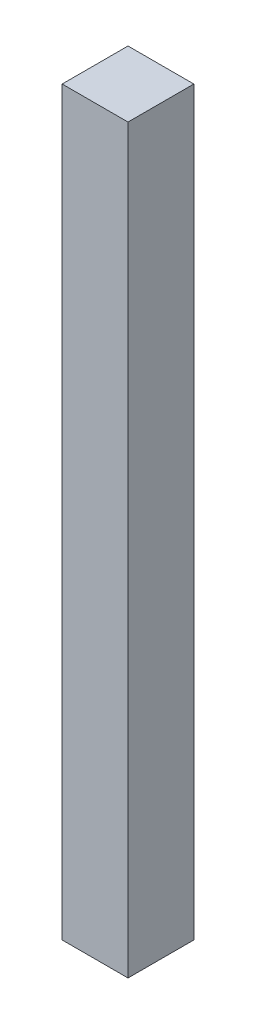
SolidWorks part; units mm, degrees
ref_plane "Front Plane" through (0, 0, 0) normal (0, 0, 1) x (1, 0, 0)
ref_plane "Top Plane" through (0, 0, 0) normal (0, 1, 0) x (1, 0, 0)
ref_plane "Right Plane" through (0, 0, 0) normal (1, 0, 0) x (0, 0, -1)
sketch "Sketch1" plane through (0, 0, 0) normal (0, 1, 0) x (1, 0, 0)
  line L1 (0, 0) -> (25.4, 0)
  line L2 (0, 0) -> (0, 25.4)
  line L3 (0, 25.4) -> (25.4, 25.4)
  line L4 (25.4, 0) -> (25.4, 25.4)
  dimension "D1" = 25.4
  dimension "D2" = 25.4
extrude "Boss-Extrude1" add sketch "Sketch1" along normal blind 609.6
sketch "Sketch3" plane through (0, 0, -25.4) normal (0, 0, -1) x (-1, 0, 0)
  line L0 (0, 609.6) -> (0, 0) construction
  line L1 (0, 466.3042) -> (-25.4, 466.3042)
  line L2 (0, 466.3042) -> (0, 609.6)
  line L3 (0, 609.6) -> (-25.4, 609.6)
  line L4 (-25.4, 466.3042) -> (-25.4, 609.6)
  line L6 (-25.4, 466.3042) -> (0, 466.3042) construction
extrude "Cut-Extrude1" [suppressed] cut sketch "Sketch3" against normal up to surface (25.4 mm away) up to face at (12.7, 304.8, 0)
sketch "Sketch4" [suppressed] plane through (0, 0, 0) normal (0, 0, 1) x (1, 0, 0)
  line L0 (0, 609.6) -> (0, 0) construction
  line L1 (0, 276.4933) -> (25.4, 276.4933)
  line L2 (0, 276.4933) -> (0, 609.6)
  line L3 (0, 609.6) -> (25.4, 609.6)
  line L4 (25.4, 276.4933) -> (25.4, 609.6)
  line L6 (0, 276.4933) -> (25.4, 276.4933) construction
extrude "Cut-Extrude2" [suppressed] cut sketch "Sketch4" against normal up to surface (430.6021 mm away) up to face at (12.7, 304.8, -25.4)
sketch "Sketch5" plane through (0, 0, -25.4) normal (0, 0, -1) x (-1, 0, 0)
  line L0 (0, 609.6) -> (0, 0) construction
  line L1 (0, 571.9407) -> (-25.4, 571.9407)
  line L2 (0, 571.9407) -> (0, 609.6)
  line L3 (0, 609.6) -> (-25.4, 609.6)
  line L4 (-25.4, 571.9407) -> (-25.4, 609.6)
extrude "Cut-Extrude3" cut sketch "Sketch5" against normal up to surface (25.4 mm away) up to face at (12.7, 304.8, 0)
sketch "Sketch6" [suppressed] plane through (0, 0, -25.4) normal (0, 0, -1) x (-1, 0, 0)
  line L0 (0, 609.6) -> (0, 0) construction
  line L1 (0, 553.696) -> (-25.4, 553.696)
  line L2 (0, 553.696) -> (0, 609.6)
  line L3 (0, 609.6) -> (-25.4, 609.6)
  line L4 (-25.4, 553.696) -> (-25.4, 609.6)
  line L6 (-25.4, 553.696) -> (0, 553.696) construction
extrude "Cut-Extrude4" [suppressed] cut sketch "Sketch6" against normal up to surface (25.4 mm away) up to face at (12.7, 285.9703, 0)
sketch "Sketch7" [suppressed] plane through (0, 0, 0) normal (0, 0, 1) x (1, 0, 0)
  line L0 (25.4, 609.6) -> (25.4, 0) construction
  line L1 (25.4, 422.1079) -> (0, 422.1079)
  line L2 (25.4, 422.1079) -> (25.4, 609.6)
  line L3 (25.4, 609.6) -> (0, 609.6)
  line L4 (0, 422.1079) -> (0, 609.6)
  line L8 (0, 422.1079) -> (25.4, 422.1079) construction
extrude "Cut-Extrude5" [suppressed] cut sketch "Sketch7" against normal up to surface (25.4 mm away) up to face at (12.7, 285.9703, -25.4)
sketch "Sketch8" [suppressed] plane through (0, 0, -25.4) normal (0, 0, -1) x (-1, 0, 0)
  line L0 (0, 609.6) -> (0, 0) construction
  line L1 (0, 319.3022) -> (-25.4, 319.3022)
  line L2 (0, 319.3022) -> (0, 609.6)
  line L3 (0, 609.6) -> (-25.4, 609.6)
  line L4 (-25.4, 319.3022) -> (-25.4, 609.6)
  line L6 (-25.4, 319.3022) -> (0, 319.3022) construction
extrude "Cut-Extrude6" [suppressed] cut sketch "Sketch8" against normal up to surface (25.4 mm away) up to face at (12.7, 285.9703, 0)
sketch "Sketch9" [suppressed] plane through (0, 0, 0) normal (0, 0, 1) x (1, 0, 0)
  line L0 (0, 609.6) -> (0, 0) construction
  line L1 (0, 329.8783) -> (25.4, 329.8783)
  line L2 (0, 329.8783) -> (0, 609.6)
  line L3 (0, 609.6) -> (25.4, 609.6)
  line L4 (25.4, 329.8783) -> (25.4, 609.6)
  line L6 (0, 329.8783) -> (25.4, 329.8783) construction
extrude "Cut-Extrude7" [suppressed] cut sketch "Sketch9" against normal up to surface (25.4 mm away) up to face at (12.7, 285.9703, -25.4)
sketch "Sketch10" [suppressed] plane through (25.4, 0, 0) normal (1, 0, 0) x (0, 0, -1)
  line L1 (25.4, 329.8783) -> (0, 329.8783)
  line L2 (25.4, 329.8783) -> (25.4, 0)
  line L3 (25.4, 0) -> (0, 0)
  line L4 (0, 329.8783) -> (0, 0)
extrude "Boss-Extrude2" [suppressed] add sketch "Sketch10" along normal blind 25.4
sketch "Sketch11" [suppressed] plane through (0, 0, -25.4) normal (0, 0, -1) x (-1, 0, 0)
  line L1 (0, 329.8783) -> (-50.8, 329.8783)
  line L2 (0, 329.8783) -> (0, 0)
  line L3 (0, 0) -> (-50.8, 0)
  line L4 (-50.8, 329.8783) -> (-50.8, 0)
extrude "Boss-Extrude3" [suppressed] add sketch "Sketch11" along normal blind 25.4
sketch "Sketch12" [suppressed] plane through (0, 0, 0) normal (0, 0, 1) x (1, 0, 0)
  line L1 (25.4, 319.3022) -> (0, 319.3022)
  line L2 (25.4, 319.3022) -> (25.4, 0)
  line L3 (25.4, 0) -> (0, 0)
  line L4 (0, 319.3022) -> (0, 0)
extrude "Boss-Extrude4" [suppressed] add sketch "Sketch12" along normal blind 25.4
sketch "Sketch13" [suppressed] plane through (25.4, 0, 0) normal (1, 0, 0) x (0, 0, -1)
  line L0 (-25.4, 0) -> (25.4, 0) construction
  line L1 (25.4, 319.3022) -> (-25.4, 319.3022)
  line L2 (25.4, 319.3022) -> (25.4, 0)
  line L3 (25.4, 0) -> (-25.4, 0)
  line L4 (-25.4, 319.3022) -> (-25.4, 0)
  line L5 (-25.4, 0) -> (-25.4, 319.3022) construction
extrude "Boss-Extrude5" [suppressed] add sketch "Sketch13" along normal blind 25.4
sketch "Sketch14" [suppressed] plane through (0, 0, -25.4) normal (0, 0, -1) x (-1, 0, 0)
  line L0 (-25.4, 422.1079) -> (-25.4, 0) construction
  line L1 (-25.4, 422.1079) -> (0, 422.1079)
  line L2 (-25.4, 422.1079) -> (-25.4, 0)
  line L3 (-25.4, 0) -> (0, 0)
  line L4 (0, 422.1079) -> (0, 0)
extrude "Boss-Extrude6" [suppressed] add sketch "Sketch14" along normal blind 25.4
sketch "Sketch15" [suppressed] plane through (25.4, 0, 0) normal (1, 0, 0) x (0, 0, -1)
  line L1 (50.8, 422.1079) -> (0, 422.1079)
  line L2 (50.8, 422.1079) -> (50.8, 0)
  line L3 (50.8, 0) -> (0, 0)
  line L4 (0, 422.1079) -> (0, 0)
extrude "Boss-Extrude7" [suppressed] add sketch "Sketch15" along normal blind 25.4
sketch "Sketch16" plane through (0, 0, 0) normal (0, 0, 1) x (1, 0, 0)
  line L1 (25.4, 571.9407) -> (0, 571.9407)
  line L2 (25.4, 571.9407) -> (25.4, 0)
  line L3 (25.4, 0) -> (0, 0)
  line L4 (0, 571.9407) -> (0, 0)
extrude "Boss-Extrude8" add sketch "Sketch16" along normal blind 25.4
sketch "Sketch17" plane through (25.4, 0, 0) normal (1, 0, 0) x (0, 0, -1)
  line L1 (25.4, 571.9407) -> (-25.4, 571.9407)
  line L2 (25.4, 571.9407) -> (25.4, 0)
  line L3 (25.4, 0) -> (-25.4, 0)
  line L4 (-25.4, 571.9407) -> (-25.4, 0)
extrude "Boss-Extrude9" add sketch "Sketch17" along normal blind 25.4
sketch "Sketch18" [suppressed] plane through (0, 0, -25.4) normal (0, 0, -1) x (-1, 0, 0)
  line L1 (0, 276.4933) -> (-25.4, 276.4933)
  line L2 (0, 276.4933) -> (0, 0)
  line L3 (0, 0) -> (-25.4, 0)
  line L4 (-25.4, 276.4933) -> (-25.4, 0)
extrude "Boss-Extrude10" [suppressed] add sketch "Sketch18" along normal blind 25.4
sketch "Sketch19" [suppressed] plane through (25.4, 0, 0) normal (1, 0, 0) x (0, 0, -1)
  line L1 (50.8, 276.4933) -> (0, 276.4933)
  line L2 (50.8, 276.4933) -> (50.8, 0)
  line L3 (50.8, 0) -> (0, 0)
  line L4 (0, 276.4933) -> (0, 0)
extrude "Boss-Extrude11" [suppressed] add sketch "Sketch19" along normal blind 25.4
sketch "Sketch22" [suppressed] plane through (25.4, 0, 0) normal (1, 0, 0) x (0, 0, -1)
  line L1 (0, 553.696) -> (25.4, 553.696)
  line L2 (0, 553.696) -> (0, 0)
  line L3 (0, 0) -> (25.4, 0)
  line L4 (25.4, 553.696) -> (25.4, 0)
extrude "Boss-Extrude14" [suppressed] add sketch "Sketch22" along normal blind 25.4
sketch "Sketch23" [suppressed] plane through (0, 0, -25.4) normal (0, 0, -1) x (-1, 0, 0)
  line L1 (-50.8, 553.696) -> (0, 553.696)
  line L2 (-50.8, 553.696) -> (-50.8, 0)
  line L3 (-50.8, 0) -> (0, 0)
  line L4 (0, 553.696) -> (0, 0)
extrude "Boss-Extrude15" [suppressed] add sketch "Sketch23" along normal blind 25.4
sketch "Sketch24" [suppressed] plane through (0, 0, 0) normal (0, 0, 1) x (1, 0, 0)
  line L0 (25.4, 466.3042) -> (25.4, 0) construction
  line L1 (0, 466.3042) -> (25.4, 466.3042)
  line L2 (0, 466.3042) -> (0, 0)
  line L3 (0, 0) -> (25.4, 0)
  line L4 (25.4, 466.3042) -> (25.4, 0)
extrude "Boss-Extrude16" [suppressed] add sketch "Sketch24" along normal blind 25.4
sketch "Sketch25" [suppressed] plane through (25.4, 0, 0) normal (1, 0, 0) x (0, 0, -1)
  line L1 (-25.4, 0) -> (25.4, 0)
  line L2 (-25.4, 0) -> (-25.4, 466.3042)
  line L3 (-25.4, 466.3042) -> (25.4, 466.3042)
  line L4 (25.4, 0) -> (25.4, 466.3042)
extrude "Boss-Extrude17" [suppressed] add sketch "Sketch25" along normal blind 25.4
sketch "Sketch26" [suppressed] plane through (0, 329.8783, 0) normal (0, 1, 0) x (1, 0, 0)
  line L0 (0, 50.8) -> (50.8, 50.8) construction
  line L1 (50.8, 0) -> (25.4, 0)
  line L2 (50.8, 0) -> (50.8, 50.8)
  line L4 (25.4, 0) -> (25.4, 25.4)
  line L5 (0, 50.8) -> (0, 0) construction
  line L6 (50.8, 50.8) -> (0, 50.8)
  line L8 (25.4, 25.4) -> (0, 25.4)
  line L9 (0, 50.8) -> (0, 25.4)
  dimension "D1" = 25.4
  dimension "D2" = 25.4
extrude "Cut-Extrude8" [suppressed] cut sketch "Sketch26" against normal up to surface (329.8783 mm away)
sketch "Sketch27" [suppressed] plane through (0, 466.3042, 0) normal (0, 1, 0) x (1, 0, 0)
  line L1 (50.8, -25.4) -> (0, -25.4)
  line L2 (50.8, -25.4) -> (50.8, 0)
  line L3 (50.8, 0) -> (0, 0)
  line L4 (0, -25.4) -> (0, 0)
extrude "Cut-Extrude9" [suppressed] cut sketch "Sketch27" against normal up to surface (466.3042 mm away)
sketch "Sketch28" [suppressed] plane through (0, 276.4933, 0) normal (0, 1, 0) x (1, 0, 0)
  line L0 (0, 50.8) -> (0, 0) construction
  line L1 (50.8, 50.8) -> (0, 50.8)
  line L2 (50.8, 50.8) -> (50.8, 25.4)
  line L3 (50.8, 25.4) -> (0, 25.4)
  line L4 (0, 50.8) -> (0, 25.4)
extrude "Cut-Extrude10" [suppressed] cut sketch "Sketch28" against normal up to surface (276.4933 mm away)
sketch "Sketch29" [suppressed] plane through (0, 553.696, 0) normal (0, 1, 0) x (1, 0, 0)
  line L0 (0, 0) -> (0, 50.8) construction
  line L1 (50.8, 50.8) -> (0, 50.8)
  line L2 (50.8, 50.8) -> (50.8, 25.4)
  line L3 (50.8, 25.4) -> (0, 25.4)
  line L4 (0, 50.8) -> (0, 25.4)
extrude "Cut-Extrude11" [suppressed] cut sketch "Sketch29" against normal up to surface (553.696 mm away)
sketch "Sketch30" [suppressed] plane through (0, 0, -25.4) normal (0, 0, -1) x (-1, 0, 0)
  line L1 (-50.8, 276.4933) -> (0, 276.4933)
  line L2 (-50.8, 276.4933) -> (-50.8, 0)
  line L3 (-50.8, 0) -> (0, 0)
  line L4 (0, 276.4933) -> (0, 0)
extrude "Boss-Extrude18" [suppressed] add sketch "Sketch30" along normal blind 25.4
sketch "Sketch31" [suppressed] plane through (0, 276.4933, 0) normal (0, 1, 0) x (1, 0, 0)
  line L0 (0, 50.8) -> (0, 0) construction
  line L1 (50.8, 50.8) -> (0, 50.8)
  line L2 (50.8, 50.8) -> (50.8, 25.4)
  line L3 (50.8, 25.4) -> (0, 25.4)
  line L4 (0, 50.8) -> (0, 25.4)
extrude "Cut-Extrude12" [suppressed] cut sketch "Sketch31" against normal up to surface (276.4933 mm away)
